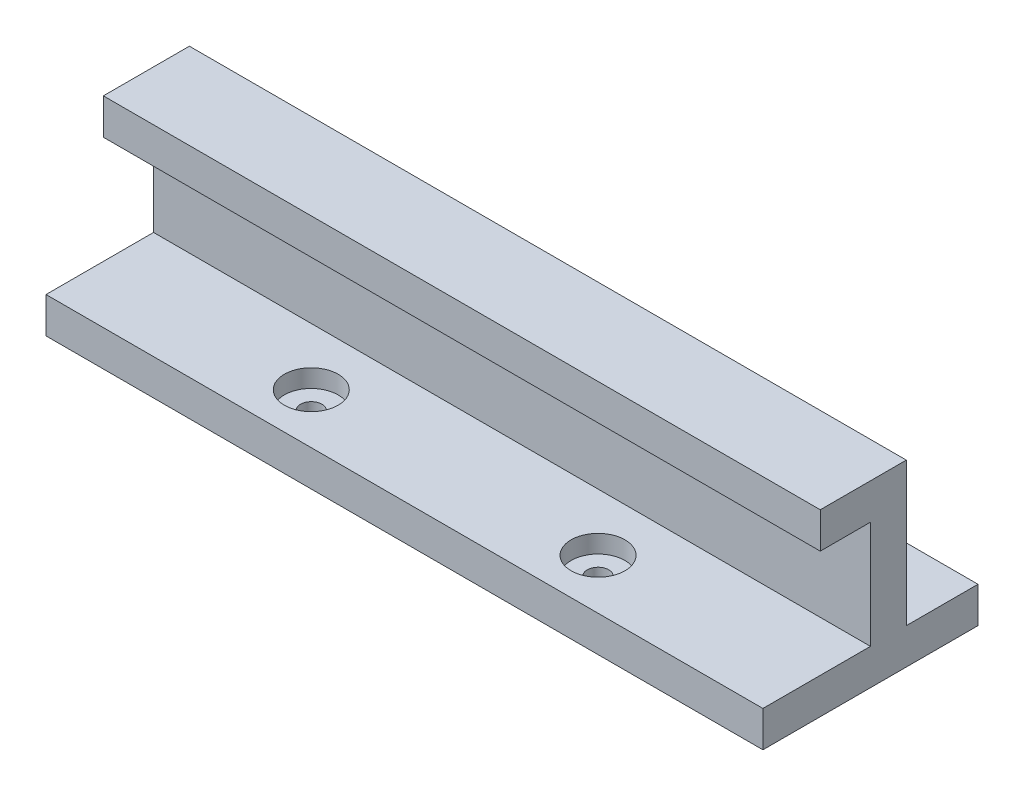
SolidWorks part; units mm, degrees
ref_plane "Front Plane" through (0, 0, 0) normal (0, 0, 1) x (1, 0, 0)
ref_plane "Top Plane" through (0, 0, 0) normal (0, 1, 0) x (1, 0, 0)
ref_plane "Right Plane" through (0, 0, 0) normal (1, 0, 0) x (0, 0, -1)
sketch "Sketch1" plane through (0, 0, 0) normal (0, 1, 0) x (1, 0, 0)
  line L0 (50, 20) -> (50, 0) construction
  line L1 (0, 0) -> (100, 0)
  line L2 (0, 0) -> (0, 20)
  line L3 (0, 20) -> (100, 20)
  line L4 (100, 0) -> (100, 20)
  circle A0 centre (30, 7) radius 1.5
  circle A1 centre (70, 7) radius 1.5
  dimension "D3" = 3
  dimension "D4" = 3
  dimension "D1" = 20
  dimension "D2" = 100
  dimension "D5" = 7
  dimension "D6" = 7
  dimension "D7" = 40
  dimension "D8" = 20
extrude "Extrude-Base" add sketch "Sketch1" along normal blind 5
sketch "Sketch2" plane through (0, 5, 0) normal (0, 1, 0) x (1, 0, 0)
  line L0 (100, 0) -> (100, 20) construction
  line L1 (0, 20) -> (100, 20)
  line L2 (0, 20) -> (0, 15)
  line L3 (0, 15) -> (100, 15)
  line L4 (100, 20) -> (100, 15)
  dimension "D1" = 5
extrude "Extrude-Vertical clamp" add sketch "Sketch2" along normal blind 20
sketch "Sketch3" plane through (0, 0, -15) normal (0, 0, 1) x (1, 0, 0)
  line L0 (100, 25) -> (100, 5) construction
  line L1 (0, 25) -> (100, 25)
  line L2 (0, 25) -> (0, 20)
  line L3 (0, 20) -> (100, 20)
  line L4 (100, 25) -> (100, 20)
  dimension "D1" = 5
extrude "Extrude-Clamp Roof" add sketch "Sketch3" along normal blind 7
sketch "Sketch5" plane through (0, 0, 0) normal (0, 1, 0) x (1, 0, 0)
  line L0 (100, 20) -> (100, 30)
  line L1 (100, 30) -> (0, 30)
  line L2 (0, 30) -> (0, 20)
  line L3 (0, 20) -> (100, 20)
  line L4 (50, 20) -> (50, 30) construction
  circle A0 centre (70, 25) radius 1.5
  circle A1 centre (30, 25) radius 1.5
  dimension "D2" = 20
  dimension "D6" = 3
  dimension "D7" = 3
  dimension "D1" = 10
  dimension "D3" = 20
  dimension "D4" = 5
  dimension "D5" = 5
extrude "Boss-Extrude4" add sketch "Sketch5" along normal blind 5
sketch "Sketch4" plane through (0, 5, 0) normal (0, 1, 0) x (1, 0, 0)
  circle A0 centre (30, 7) radius 3.75
  circle A1 centre (70, 7) radius 3.75
  circle A2 centre (30, 7) radius 1.5 construction
  circle A3 centre (70, 7) radius 1.5 construction
  circle A4 centre (30, 25) radius 3.75
  circle A5 centre (70, 25) radius 3.75
  dimension "D1" = 7.5
  dimension "D2" = 7.5
  dimension "D3" = 7.5
  dimension "D4" = 7.5
extrude "Cut-Extrude1" cut sketch "Sketch4" against normal blind 2.5
equation "\"screwInset\"=7.5"
equation "\"D1@Sketch4\"=\"screwInset\""
equation "\"D2@Sketch4\"=\"screwInset\""
equation "\"D3@Sketch4\"=\"screwInset\""
equation "\"D4@Sketch4\"=\"screwInset\""
